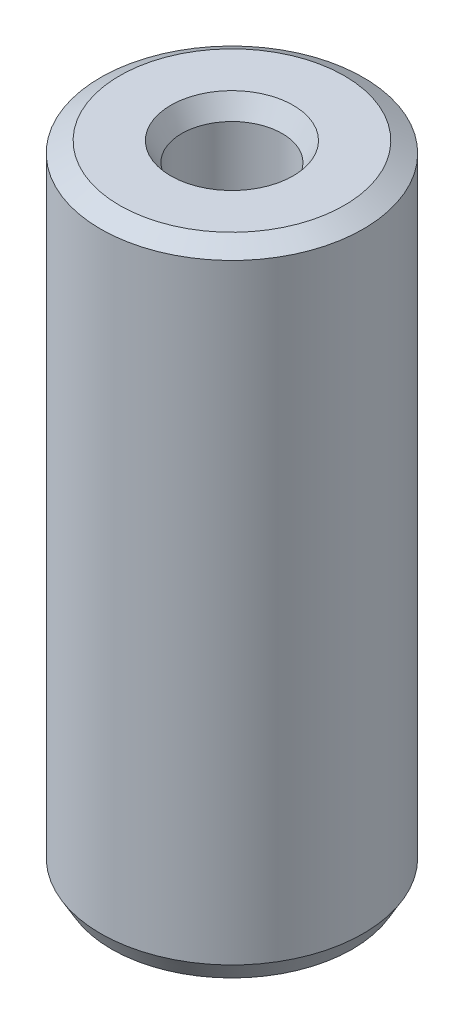
SolidWorks part; units mm, degrees
ref_plane "Front Plane" through (0, 0, 0) normal (0, 0, 1) x (1, 0, 0)
ref_plane "Top Plane" through (0, 0, 0) normal (0, 1, 0) x (1, 0, 0)
ref_plane "Right Plane" through (0, 0, 0) normal (1, 0, 0) x (0, 0, -1)
sketch "Sketch1" plane through (0, 0, 0) normal (0, 1, 0) x (1, 0, 0)
  circle A0 centre (0, 0) radius 32.5
  dimension "SLEEVE_OD" = 65
extrude "Boss-Extrude1" add sketch "Sketch1" along normal blind 158.3863
sketch "Sketch2" plane through (0, 0, 0) normal (0, 1, 0) x (1, 0, 0)
  circle A0 centre (0, 0) radius 12.434
  dimension "BORE_D" = 24.868
extrude "Cut-Extrude1" cut sketch "Sketch2" along normal through all
chamfer "Chamfer1" distance 2.7147 angle 60 4 edges at (0, 158.3863, 12.434) (0, 0, 12.434) (0, 0, 32.5) (0, 158.3863, 32.5) first distance on face at (0, 158.3863, 12.434) first distance on face at (0, 0, 12.434) first distance on face at (0, 158.3863, 32.5)
